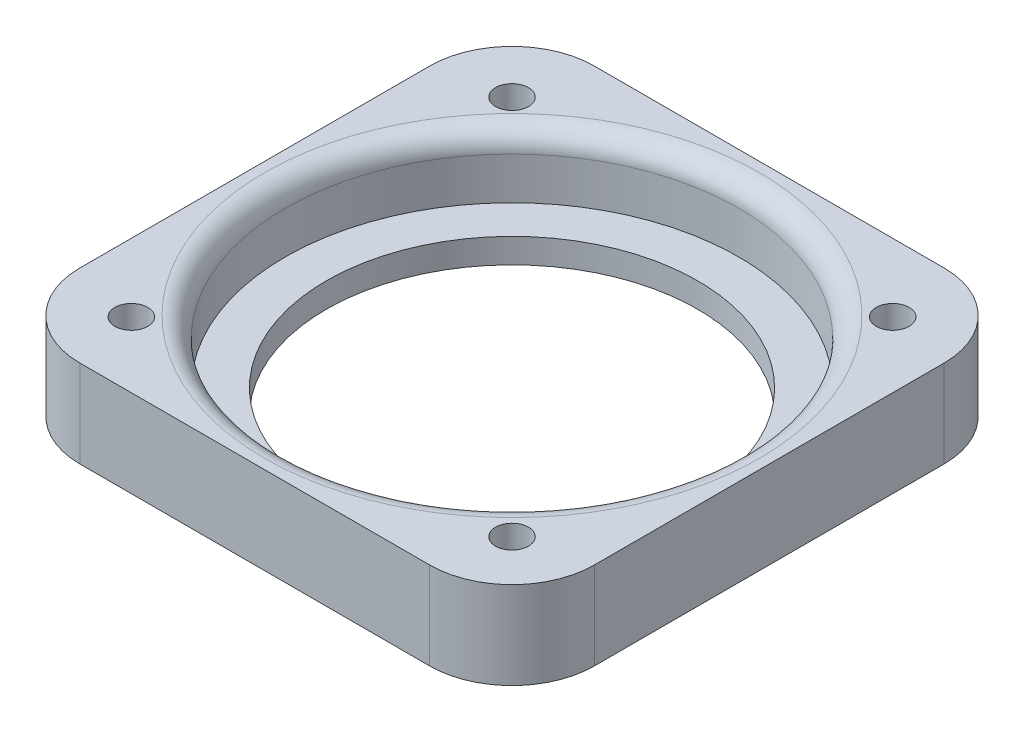
SolidWorks part; units mm, degrees
ref_plane "前视基准面" through (0, 0, 0) normal (0, 0, 1) x (1, 0, 0)
ref_plane "上视基准面" through (0, 0, 0) normal (0, 1, 0) x (1, 0, 0)
ref_plane "右视基准面" through (0, 0, 0) normal (1, 0, 0) x (0, 0, -1)
sketch "草图1" plane through (0, 0, 0) normal (0, 1, 0) x (1, 0, 0)
  circle A0 centre (0, 0) radius 25
extrude "凸台-拉伸1" add sketch "草图1" along normal blind 8.5
sketch "草图2" plane through (0, 8.5, 0) normal (0, 1, 0) x (1, 0, 0)
  circle A0 centre (0, 0) radius 22.05
  dimension "D1" = 44.1
extrude "切除-拉伸1" cut sketch "草图2" against normal blind 6.1
sketch "草图3" plane through (0, 2.4, 0) normal (0, 1, 0) x (1, 0, 0)
  circle A0 centre (0, 0) radius 18.05
  circle A1 centre (0, 0) radius 22.05 construction
  dimension "D1" = 4
extrude "切除-拉伸2" cut sketch "草图3" against normal blind 12.5
sketch "草图4" plane through (0, 0, 0) normal (0, 1, 0) x (1, 0, 0)
  line L1 (-25, 25) -> (25, 25)
  line L2 (-25, 25) -> (-25, -25)
  line L3 (-25, -25) -> (25, -25)
  line L4 (25, 25) -> (25, -25)
  line L5 (-25, 25) -> (25, -25) construction
  line L6 (-25, -25) -> (25, 25) construction
  circle A0 centre (0, 0) radius 25
  circle A1 centre (-18.3848, 18.3848) radius 1.5
  circle A2 centre (18.6152, 18.3848) radius 1.5
  circle A3 centre (18.6152, -18.6152) radius 1.5
  circle A4 centre (-18.3848, -18.6152) radius 1.5
  point P0 (0, 0)
  point P20 (0.1152, -0.1152)
  dimension "D3" = 3
  dimension "D4" = 26
  dimension "D6" = 37
  dimension "D7" = 37
  dimension "D1" = 50
  dimension "D2" = 50
  dimension "D5" = 4
extrude "凸台-拉伸2" add sketch "草图4" along normal blind 8.5 contours A0 L1 L2 | A0 L4 L1 | A0 L2 L3 | A0 L3 L4 region at (-19.4617, 0, -19.4617) region at (12.5, 0, -24.6464) region at (-23.5702, 0, 9.3406) region at (24.6464, 0, 12.5)
fillet "圆角1" radius 8 4 edges at (-25, 4.25, 25) (25, 4.25, 25) (25, 4.25, -25) (-25, 4.25, -25)
sketch "草图5" plane through (0, 8.5, 0) normal (0, 1, 0) x (1, 0, 0)
  circle A0 centre (-18.3848, 18.3848) radius 1.6
  circle A1 centre (18.6152, 18.3848) radius 1.6
  circle A2 centre (18.6152, -18.6152) radius 1.6
  circle A3 centre (-18.3848, -18.6152) radius 1.6
  point P12 (0.1152, -0.1152)
  dimension "D2" = 3.2
  dimension "D1" = 4
extrude "切除-拉伸3" cut sketch "草图5" against normal blind 15
fillet "圆角2" radius 2 1 edges at (0, 8.5, 22.05)
sketch "草图6" plane through (0, 0, 0) normal (0, -1, 0) x (1, 0, 0)
  circle A0 centre (-18.3848, 18.6152) radius 3.2
extrude "切除-拉伸4" cut sketch "草图6" against normal blind 2
pattern_circular "阵列(圆周)1" count 4 over 360 about axis through (0, 0, 0) along (0, 1, 0) of "切除-拉伸4"
